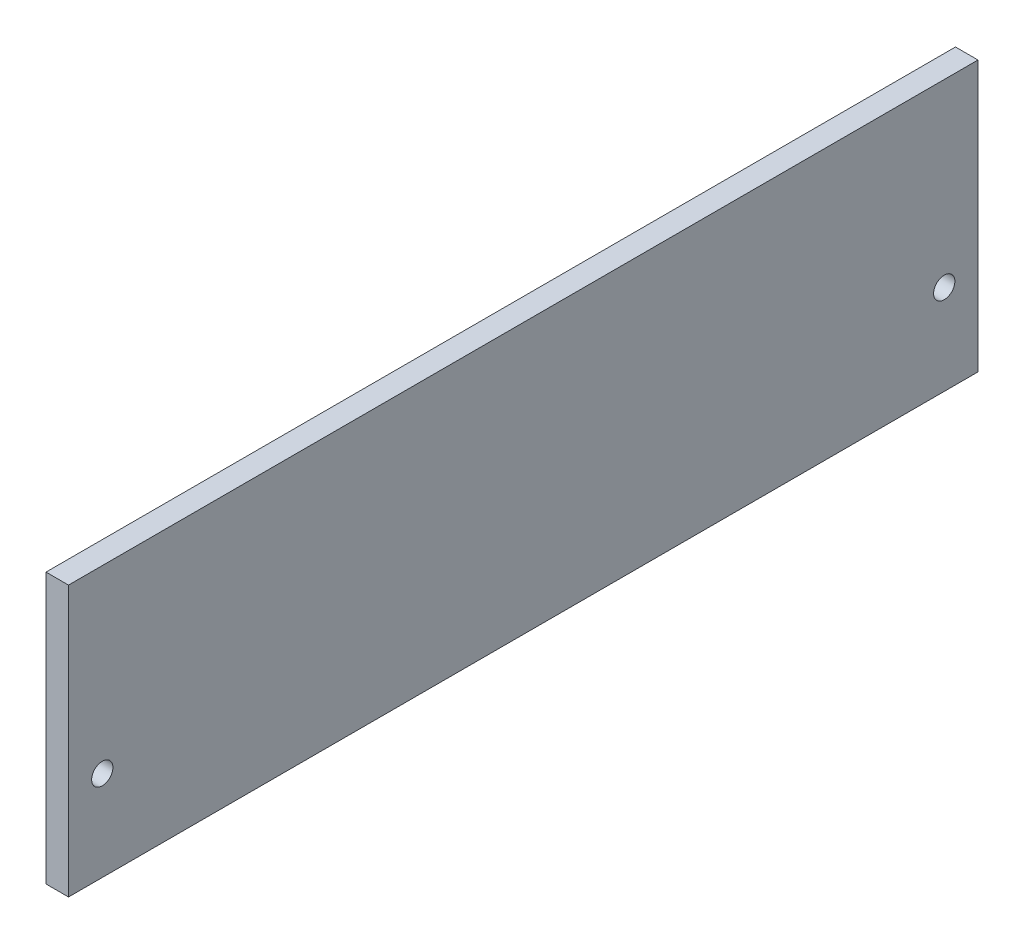
SolidWorks part; units mm, degrees
ref_plane "Front Plane" through (0, 0, 0) normal (0, 0, 1) x (1, 0, 0)
ref_plane "Top Plane" through (0, 0, 0) normal (0, 1, 0) x (1, 0, 0)
ref_plane "Right Plane" through (0, 0, 0) normal (1, 0, 0) x (0, 0, -1)
sketch "Sketch1" plane through (0, 0, 0) normal (1, 0, 0) x (0, 0, -1)
  line L0 (-59.3725, -6.35) -> (59.3725, -6.35) construction
  line L1 (64.135, 19.05) -> (-64.135, 19.05)
  line L2 (64.135, 19.05) -> (64.135, -19.05)
  line L3 (64.135, -19.05) -> (-64.135, -19.05)
  line L4 (-64.135, 19.05) -> (-64.135, -19.05)
  line L5 (64.135, 19.05) -> (-64.135, -19.05) construction
  line L6 (64.135, -19.05) -> (-64.135, 19.05) construction
  line L7 (0, -6.35) -> (0, 0) construction
  circle A0 centre (-59.3725, -6.35) radius 1.5
  circle A1 centre (59.3725, -6.35) radius 1.5
  point P0 (0, 0)
  point P15 (-57.785, -9.8036)
  dimension "D1" = 3
  dimension "D2" = 4.7625
  dimension "D3" = 128.27
  dimension "D4" = 12.7
  dimension "D5" = 25.4
extrude "Boss-Extrude1" add sketch "Sketch1" along normal blind 3.175
